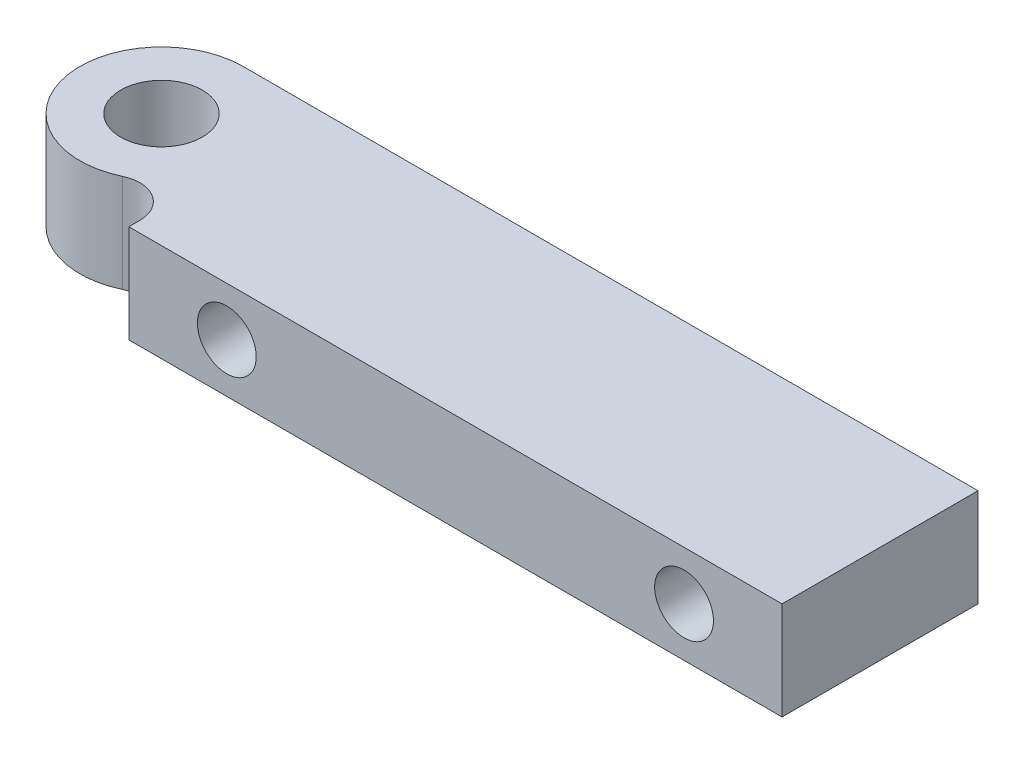
SolidWorks part; units mm, degrees
ref_plane "Front Plane" through (0, 0, 0) normal (0, 0, 1) x (1, 0, 0)
ref_plane "Top Plane" through (0, 0, 0) normal (0, 1, 0) x (1, 0, 0)
ref_plane "Right Plane" through (0, 0, 0) normal (1, 0, 0) x (0, 0, -1)
sketch "Sketch1" plane through (0, 0, 0) normal (0, 1, 0) x (1, 0, 0)
  line L0 (0, 6.35) -> (12.3665, 6.35)
  line L1 (12.3665, 6.35) -> (57.15, 6.35)
  line L2 (6.35, 0) -> (6.35, -8.89)
  line L3 (6.35, -8.89) -> (57.15, -8.89)
  line L4 (57.15, 6.35) -> (57.15, -8.89)
  circle A0 centre (0, 0) radius 3.175
  arc A1 (0, 6.35) -> (6.35, 0) centre (0, 0) ccw
  dimension "D1" = 12.7
  dimension "D2" = 6.35
  dimension "D3" = 6.35
  dimension "D4" = 50.8
  dimension "D5" = 15.24
extrude "Boss-Extrude1" add sketch "Sketch1" along normal mid plane 7.62
fillet "Fillet1" radius 2.54 1 edges at (6.35, 0, 0)
sketch "Sketch2" plane through (0, 0, 8.89) normal (0, 0, 1) x (1, 0, 0)
  circle A0 centre (49.53, 0) radius 2.5908 construction
  circle A1 centre (13.97, 0) radius 2.5908 construction
  circle A2 centre (49.53, 0) radius 2.5908
  circle A3 centre (13.97, 0) radius 2.5908
  circle A4 centre (13.97, 0) radius 2.286
  circle A5 centre (49.53, 0) radius 2.286
  dimension "D1" = 4.572
  dimension "D2" = 4.572
extrude "Cut-Extrude1" cut sketch "Sketch2" against normal blind 5.08 contours A4 | A5 region at (13.97, 0, 8.89) region at (49.53, 0, 8.89)
